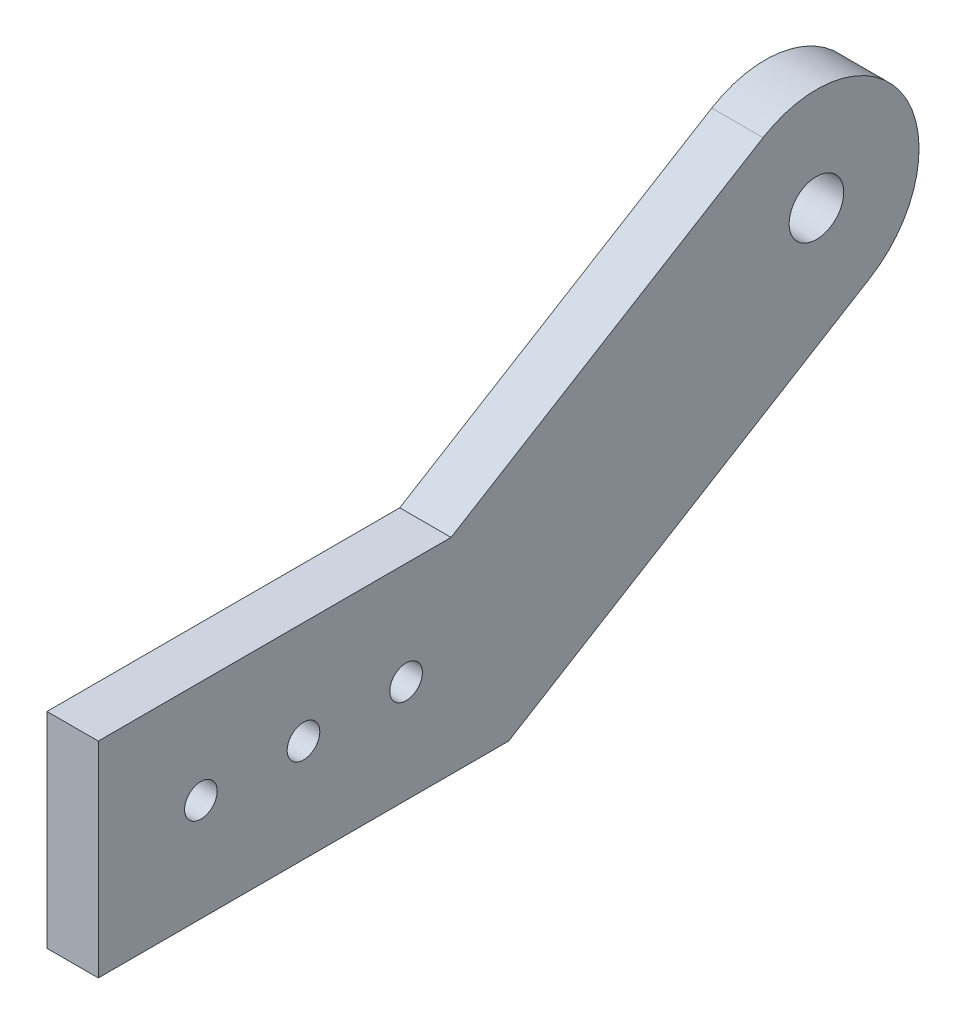
SolidWorks part; units mm, degrees
material "6061-T6 (SS)"
ref_plane "Front" through (0, 0, 0) normal (0, 0, 1) x (1, 0, 0)
ref_plane "Top" through (0, 0, 0) normal (0, 1, 0) x (1, 0, 0)
ref_plane "Right" through (0, 0, 0) normal (1, 0, 0) x (0, 0, -1)
sketch "Sketch1" plane through (0, 0, 0) normal (1, 0, 0) x (0, 0, -1)
  line L0 (50.8, 0) -> (95.5106, 27.2561)
  line L1 (0, 0) -> (50.8, 0)
  line L2 (0, 0) -> (0, 25.4)
  line L3 (0, 25.4) -> (43.6683, 25.4)
  line L5 (82.2894, 48.9439) -> (43.6683, 25.4)
  arc A0 (95.5106, 27.2561) -> (82.2894, 48.9439) centre (88.9, 38.1) ccw
  dimension "D3" = 88.9
  dimension "D1" = 25.4
  dimension "D2" = 25.4
  dimension "D4" = 50.8
  dimension "D5" = 38.1
extrude "Boss-Extrude1" add sketch "Sketch1" along normal blind 6.35
hole_wizard "#10-32 Tapped Hole1" positions "Sketch2" profile "Sketch3" tap size "#10-32" standard "ANSI Inch" end condition through all
sketch "Sketch2" plane through (6.35, 0, 0) normal (1, 0, 0) x (0, 0, -1)
  line L0 (0, 0) -> (12.7, 12.7) construction
  line L1 (12.7, 12.7) -> (25.4, 12.7) construction
  line L2 (25.4, 12.7) -> (38.1, 12.7) construction
  line L3 (38.1, 12.7) -> (50.8, 25.4) construction
  line L4 (43.6683, 25.4) -> (0, 25.4) construction
  line L6 (0, 25.4) -> (0, 0) construction
  point P0 (12.7, 12.7)
  point P2 (25.4, 12.7)
  point P4 (38.1, 12.7)
  dimension "D1" = 50.8
  dimension "D2" = 12.7
sketch "Sketch3" plane through (6.35, 12.7, -12.7) normal (0, 1, 0) x (0, 0, -1)
  line L0 (0, 0) -> (0, 6.35)
  line L1 (0, 6.35) -> (2.0193, 6.35)
  line L2 (2.0193, 6.35) -> (2.0193, 0)
  line L5 (2.0193, 0) -> (0, 0)
  line L11 (0, -6.35) -> (0, 107.95) construction
  dimension "Thru Tap Drill Dia." = 4.0386
  dimension "Thru Tap Drill Depth" = 6.35
cosmetic thread "Hole Thread1"
cosmetic thread "Hole Thread2"
cosmetic thread "Hole Thread3"
hole_wizard "1/4 Clearance Hole1" positions "Sketch4" profile "Sketch5" hole size "1/4" standard "ANSI Inch" end condition through all
sketch "Sketch4" plane through (6.35, 0, 0) normal (1, 0, 0) x (0, 0, -1)
  arc A0 (95.5106, 27.2561) -> (82.2894, 48.9439) centre (88.9, 38.1) ccw construction
  point P0 (88.9, 38.1)
  point P5 (0, 0)
  point P8 (0, 0)
  point P9 (0, 0)
sketch "Sketch5" plane through (6.35, 38.1, -88.9) normal (0, 1, 0) x (0, 0, -1)
  line L0 (0, 0) -> (0, 6.35)
  line L1 (0, 6.35) -> (3.3782, 6.35)
  line L2 (3.3782, 6.35) -> (3.3782, 0)
  line L5 (3.3782, 0) -> (0, 0)
  line L11 (0, -6.35) -> (0, 107.95) construction
  dimension "Thru Hole Dia." = 6.7564
  dimension "Thru Hole Depth" = 6.35
